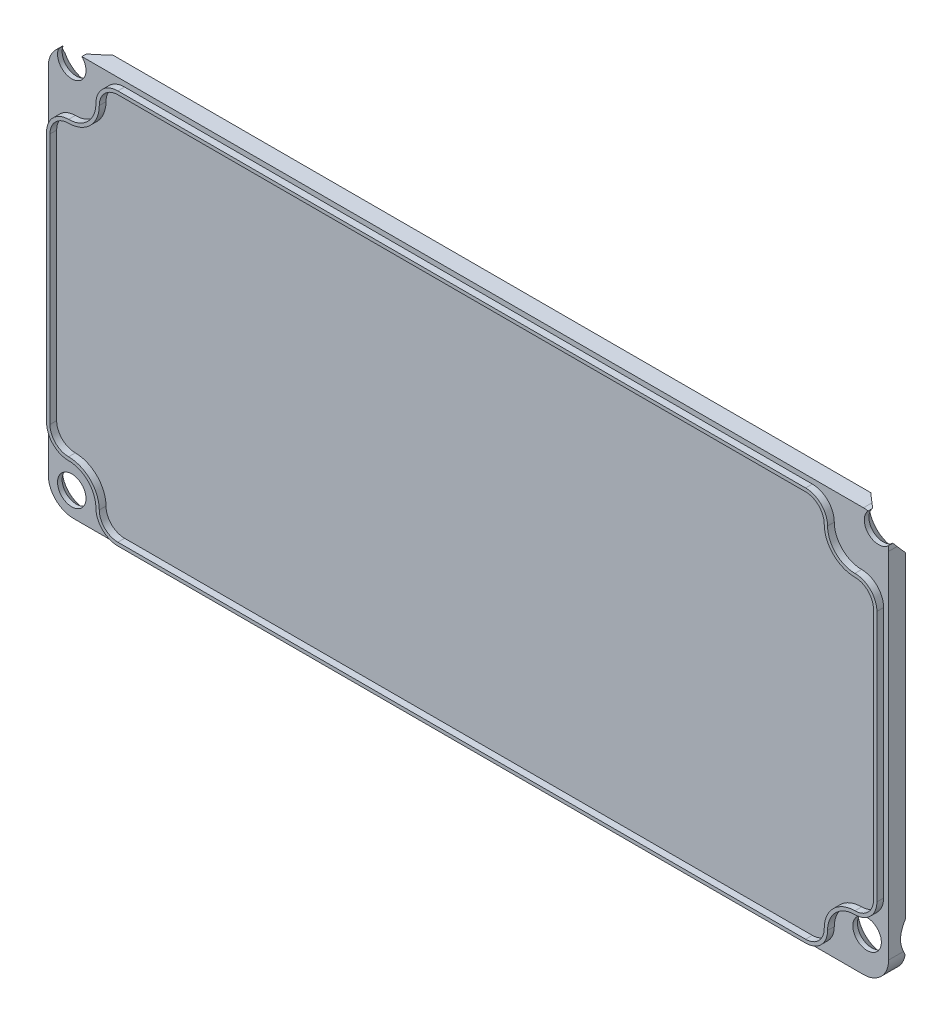
SolidWorks part; units mm, degrees
ref_plane "Plan de face" through (0, 0, 0) normal (0, 0, 1) x (1, 0, 0)
ref_plane "Plan de dessus" through (0, 0, 0) normal (0, 1, 0) x (1, 0, 0)
ref_plane "Plan de droite" through (0, 0, 0) normal (1, 0, 0) x (0, 0, -1)
sketch "Esquisse1" plane through (0, 0, 0) normal (0, 0, 1) x (1, 0, 0)
  line L0 (-50.1, -15) -> (-50.1, 21.1)
  line L1 (-47.1, 24.1) -> (47.1, 24.1)
  line L2 (50.1, 21.1) -> (50.1, -21.1)
  line L3 (47.1, -24.1) -> (-47.1, -24.1)
  line L4 (-50.1, -21.1) -> (-50.1, -15)
  arc A0 (-50.1, 21.1) -> (-47.1, 24.1) centre (-47.1, 21.1) cw
  arc A1 (47.1, 24.1) -> (50.1, 21.1) centre (47.1, 21.1) cw
  arc A2 (50.1, -21.1) -> (47.1, -24.1) centre (47.1, -21.1) cw
  arc A3 (-47.1, -24.1) -> (-50.1, -21.1) centre (-47.1, -21.1) cw
extrude "Boss.-Extru.1" add sketch "Esquisse1" along normal blind 2
sketch "Esquisse2" plane through (0, 0, 0) normal (0, 0, 1) x (1, 0, 0)
  line L0 (-41, 22.5) -> (41, 22.5) construction
  line L1 (48.5, 15) -> (48.5, -15) construction
  line L2 (41, -22.5) -> (-41, -22.5) construction
  line L3 (-48.5, -15) -> (-48.5, 15) construction
  line L4 (-49.7, -15) -> (-49.7, 15) construction
  line L5 (-41, 23.7) -> (41, 23.7) construction
  line L6 (49.7, 15) -> (49.7, -15) construction
  line L7 (41, -23.7) -> (-41, -23.7) construction
  line L8 (41, -23.3) -> (-41, -23.3)
  line L9 (-49.3, -15) -> (-49.3, 15)
  line L10 (-41, 23.3) -> (41, 23.3)
  line L11 (49.3, 15) -> (49.3, -15)
  arc A0 (41, 22.5) -> (42.62, 20.88) centre (41, 20.88) cw construction
  arc A1 (42.62, 20.88) -> (46.88, 16.62) centre (46.88, 20.88) ccw construction
  arc A2 (46.88, 16.62) -> (48.5, 15) centre (46.88, 15) cw construction
  arc A3 (48.5, -15) -> (46.88, -16.62) centre (46.88, -15) cw construction
  arc A4 (46.88, -16.62) -> (42.62, -20.88) centre (46.88, -20.88) ccw construction
  arc A5 (42.62, -20.88) -> (41, -22.5) centre (41, -20.88) cw construction
  arc A6 (-41, -22.5) -> (-42.62, -20.88) centre (-41, -20.88) cw construction
  arc A7 (-42.62, -20.88) -> (-46.88, -16.62) centre (-46.88, -20.88) ccw construction
  arc A8 (-46.88, -16.62) -> (-48.5, -15) centre (-46.88, -15) cw construction
  arc A9 (-48.5, 15) -> (-46.88, 16.62) centre (-46.88, 15) cw construction
  arc A10 (-46.88, 16.62) -> (-42.62, 20.88) centre (-46.88, 20.88) ccw construction
  arc A11 (-42.62, 20.88) -> (-41, 22.5) centre (-41, 20.88) cw construction
  arc A12 (-49.7, 15) -> (-46.88, 17.82) centre (-46.88, 15) cw construction
  arc A13 (-46.88, 17.82) -> (-43.82, 20.88) centre (-46.88, 20.88) ccw construction
  arc A14 (-43.82, 20.88) -> (-41, 23.7) centre (-41, 20.88) cw construction
  arc A15 (41, 23.7) -> (43.82, 20.88) centre (41, 20.88) cw construction
  arc A16 (43.82, 20.88) -> (46.88, 17.82) centre (46.88, 20.88) ccw construction
  arc A17 (46.88, 17.82) -> (49.7, 15) centre (46.88, 15) cw construction
  arc A18 (49.7, -15) -> (46.88, -17.82) centre (46.88, -15) cw construction
  arc A19 (46.88, -17.82) -> (43.82, -20.88) centre (46.88, -20.88) ccw construction
  arc A20 (43.82, -20.88) -> (41, -23.7) centre (41, -20.88) cw construction
  arc A21 (-41, -23.7) -> (-43.82, -20.88) centre (-41, -20.88) cw construction
  arc A22 (-43.82, -20.88) -> (-46.88, -17.82) centre (-46.88, -20.88) ccw construction
  arc A23 (-46.88, -17.82) -> (-49.7, -15) centre (-46.88, -15) cw construction
  arc A24 (-41, -23.3) -> (-43.42, -20.88) centre (-41, -20.88) cw
  arc A25 (-43.42, -20.88) -> (-46.88, -17.42) centre (-46.88, -20.88) ccw
  arc A26 (-46.88, -17.42) -> (-49.3, -15) centre (-46.88, -15) cw
  arc A27 (-49.3, 15) -> (-46.88, 17.42) centre (-46.88, 15) cw
  arc A28 (-46.88, 17.42) -> (-43.42, 20.88) centre (-46.88, 20.88) ccw
  arc A29 (-43.42, 20.88) -> (-41, 23.3) centre (-41, 20.88) cw
  arc A30 (41, 23.3) -> (43.42, 20.88) centre (41, 20.88) cw
  arc A31 (43.42, 20.88) -> (46.88, 17.42) centre (46.88, 20.88) ccw
  arc A32 (46.88, 17.42) -> (49.3, 15) centre (46.88, 15) cw
  arc A33 (49.3, -15) -> (46.88, -17.42) centre (46.88, -15) cw
  arc A34 (46.88, -17.42) -> (43.42, -20.88) centre (46.88, -20.88) ccw
  arc A35 (43.42, -20.88) -> (41, -23.3) centre (41, -20.88) cw
  dimension "D1" = 1.2
  dimension "D2" = 0.8
extrude "Extru.-Mince1" add sketch "Esquisse2" along normal blind 2.8 thin thin type mid plane wall 0.4
hole_wizard "Fraisage pour vis à tête fraisée M31" positions "Esquisse3" profile "Esquisse4" countersink size "M3" standard "Ansi Metric" end condition up to next
sketch "Esquisse3" plane through (0, 0, 0) normal (0, 0, -1) x (-1, 0, 0)
  point P0 (-48.9, 22.9)
  point P3 (47.3, 22.9)
  point P6 (47.3, -21.3)
  point P9 (-47.5338, -19.7)
sketch "Esquisse4" plane through (48.9, 22.9, 0) normal (1, 0, 0) x (0, 1, 0)
  line L0 (0, 0) -> (0, 2)
  line L1 (0, 2) -> (1.7, 2)
  line L2 (1.7, 2) -> (1.7, 1.45)
  line L3 (1.7, 1.45) -> (3.15, 0)
  line L5 (3.15, 0) -> (0, 0)
  line L6 (-1.7, 1.45) -> (-3.15, 0) construction
  line L11 (0, -6.35) -> (0, 107.95) construction
  dimension "Diamètre du perçage jusqu'au prochain" = 3.4
  dimension "Profondeur du perçage jusqu'au prochain" = 2
  dimension "Diamètre du fraisage entrant" = 6.3
  dimension "Angle du fraisage entrant" = 90
equation "\"hauteur\"=2"
equation "\"D1@Boss.-Extru.1\"=\"hauteur\""
equation "\"D1@Extru.-Mince1\"=\"hauteur\"+0.8"
